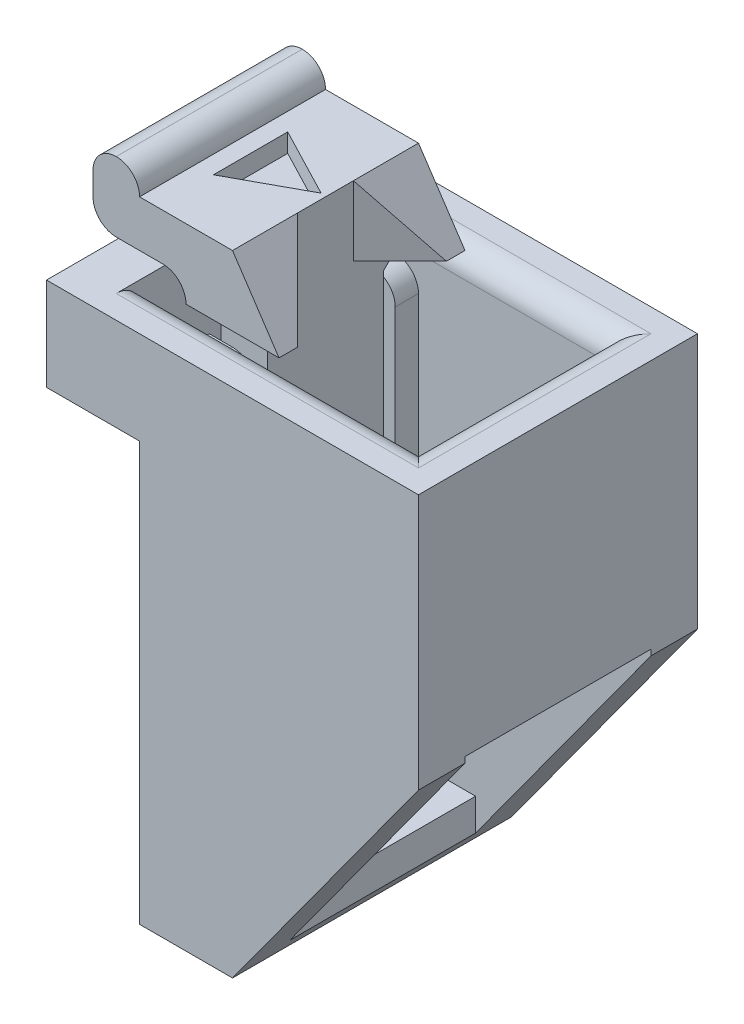
SolidWorks part; units mm, degrees
ref_plane "Front Plane" through (0, 0, 0) normal (0, 0, 1) x (1, 0, 0)
ref_plane "Top Plane" through (0, 0, 0) normal (0, 1, 0) x (1, 0, 0)
ref_plane "Right Plane" through (0, 0, 0) normal (1, 0, 0) x (0, 0, -1)
sketch "BaseSketch" plane through (0, 0, 0) normal (0, 1, 0) x (1, 0, 0)
  line L1 (-6.2677, 3.9685) -> (9.7323, 3.9685)
  line L2 (-6.2677, 3.9685) -> (-6.2677, -8.0315)
  line L3 (-6.2677, -8.0315) -> (9.7323, -8.0315)
  line L4 (9.7323, 3.9685) -> (9.7323, -8.0315)
  dimension "D1" = 16
  dimension "D2" = 12
extrude "BaseExtrude" add sketch "BaseSketch" along normal blind 2
sketch "SlotSketch" plane through (0, 2, 0) normal (0, 1, 0) x (1, 0, 0)
  line L10 (-2.2677, 0.9685) -> (-0.2677, 0.9685)
  line L11 (-2.2677, 1.9685) -> (-4.2677, 1.9685)
  line L12 (-2.2677, 1.9685) -> (-2.2677, 0.9685)
  line L13 (-0.2677, -6.0315) -> (7.7323, -6.0315)
  line L14 (7.7323, -6.0315) -> (7.7323, 1.9685)
  line L15 (-4.2677, -6.0315) -> (7.7323, -6.0315)
  line L16 (-4.2677, 1.9685) -> (-4.2677, -6.0315)
  line L17 (7.7323, 1.9685) -> (-4.2677, 1.9685)
  line L18 (7.7323, -6.0315) -> (7.7323, 1.9685)
  line L19 (-4.2677, -6.0315) -> (-2.2677, -6.0315)
  line L20 (-4.2677, 1.9685) -> (-4.2677, -6.0315)
  line L21 (7.7323, 1.9685) -> (-0.2677, 1.9685)
  line L22 (-0.2677, 1.9685) -> (-0.2677, 0.9685)
  line L23 (-2.2677, -5.0315) -> (-0.2677, -5.0315)
  line L24 (-2.2677, 0.4685) -> (-2.2677, -4.5315)
  line L25 (-2.2677, 0.4685) -> (-0.2677, 0.4685)
  line L26 (-2.2677, 0.4685) -> (-2.2677, -4.5315)
  line L27 (-2.2677, -4.5315) -> (-0.2677, -4.5315)
  line L28 (-0.2677, 0.4685) -> (-0.2677, -4.5315)
  line L29 (-0.2677, 0.4685) -> (-0.2677, -4.5315)
  line L30 (-2.2677, -5.0315) -> (-2.2677, -6.0315)
  line L31 (-0.2677, -5.0315) -> (-0.2677, -6.0315)
  line L33 (-6.2677, 3.9685) -> (9.7323, 3.9685)
  line L34 (-6.2677, 3.9685) -> (-6.2677, -8.0315)
  line L35 (-6.2677, -8.0315) -> (9.7323, -8.0315)
  line L36 (9.7323, 3.9685) -> (9.7323, -8.0315)
  line M5 (-6.2677, 3.9685) -> (-6.2677, -8.0315)
  line M6 (-6.2677, -8.0315) -> (9.7323, -8.0315)
  line M7 (9.7323, -8.0315) -> (9.7323, 3.9685)
  line M8 (9.7323, 3.9685) -> (-6.2677, 3.9685)
  dimension "D2" = 8
  dimension "D3" = 2
  dimension "D4" = 2
  dimension "D5" = 8
  dimension "D6" = 1
  dimension "D7" = 1
  dimension "D8" = 5
  dimension "D9" = 0.5
  dimension "D1" = 2
extrude "FlapExtrude" add sketch "SlotSketch" along normal blind 20.1 contours L25 L28 L27 L24
sketch "HandleBaseSketch" plane through (0, 22.1, 0) normal (0, 1, 0) x (1, 0, 0)
  line L0 (9.7323, 3.9685) -> (-6.2677, 3.9685) construction
  line L1 (-2.2677, 1.9685) -> (-0.2677, 1.9685)
  line L2 (-2.2677, 1.9685) -> (-2.2677, -6.0315)
  line L3 (-2.2677, -6.0315) -> (-0.2677, -6.0315)
  line L4 (-0.2677, 1.9685) -> (-0.2677, -6.0315)
  line L5 (-6.2677, -8.0315) -> (9.7323, -8.0315) construction
  dimension "D1" = 2
  dimension "D2" = 2
extrude "HandleBase" add sketch "HandleBaseSketch" along normal blind 3
sketch "TriangleBaseSketch" plane through (-0.2677, 0, 0) normal (1, 0, 0) x (0, 0, -1)
  line L0 (-6.0315, 22.1) -> (-3.2315, 22.1)
  line L1 (-3.2315, 22.1) -> (-3.2315, 25.1)
  line L2 (-6.0315, 25.1) -> (1.9685, 25.1) construction
  line L3 (-3.2315, 25.1) -> (-6.0315, 25.1)
  line L4 (-6.0315, 25.1) -> (-6.0315, 22.1)
  line L5 (1.9685, 22.1) -> (-0.8315, 22.1)
  line L6 (-0.8315, 22.1) -> (-0.8315, 25.1)
  line L7 (-0.8315, 25.1) -> (1.9685, 25.1)
  line L8 (1.9685, 25.1) -> (1.9685, 22.1)
extrude "PyramidExtrude" add sketch "TriangleBaseSketch" along normal blind 2.8
sketch "PyramidSideCutSketch" plane through (0, 0, -1.9685) normal (0, 0, -1) x (-1, 0, 0)
  line L0 (0.2677, 25.1) -> (0.2677, 22.1)
  line L1 (0.2677, 25.1) -> (-2.5323, 25.1)
  line L2 (-2.5323, 25.1) -> (-2.5323, 22.1)
  line L3 (-2.5323, 22.1) -> (-1.7323, 22.1)
  line L4 (-2.5323, 22.1) -> (2.2677, 22.1) construction
  line L5 (-1.7323, 22.1) -> (0.2677, 25.1)
  dimension "D1" = 2
sketch "PyramidTopCutSketch" plane through (0, 25.1, 0) normal (0, 1, 0) x (1, 0, 0)
  line L0 (-0.2677, -3.2315) -> (2.5323, -6.0315)
  line L1 (2.5323, -6.0315) -> (2.5323, -3.2315)
  line L2 (2.5323, -3.2315) -> (-0.2677, -3.2315)
  line L3 (-0.2677, -0.8315) -> (2.5323, 1.9685)
  line L4 (2.5323, 1.9685) -> (2.5323, -0.8315)
  line L5 (2.5323, -0.8315) -> (-0.2677, -0.8315)
extrude "PyramidTopCut" cut sketch "PyramidTopCutSketch" against normal blind 3
extrude "PyramidSideCut" cut sketch "PyramidSideCutSketch" against normal through all contours L1 L2 L3 L5
extrude "Boss-Extrude5" add sketch "SlotSketch<6>" along normal blind 3 contours L31 L23 L30 L19 L20 L11 L12 L10 L22 L21 L18 L13 M8 M5 M6 M7 | L12 L10 L22 L21 L18 L13 L31 L23 L30 L19 L20 L11 | L33 L36 L35 L34 region at (-1.2677, 2, -1.4685) region at (-1.2677, 2, 5.5315) region at (1.7323, 2, -3.7685)
sketch "SlotSketch<6>" plane through (0, 2, 0) normal (0, 1, 0) x (1, 0, 0) same geometry as "SlotSketch"
extrude "Sides" add sketch "SlotSketch<7>" along normal blind 20 contours L11 L20 L19 L30 L23 L31 L13 L18 L21 L22 L10 L12 | L33 L36 L35 L34
sketch "SlotSketch<7>" plane through (0, 2, 0) normal (0, 1, 0) x (1, 0, 0) same geometry as "SlotSketch"
sketch "Sketch7" plane through (-0.2677, 0, 0) normal (1, 0, 0) x (0, 0, -1)
  line L0 (-5.0315, 22) -> (-5.0315, 2) construction
  line L1 (-6.0315, 22) -> (-5.0315, 22)
  line L2 (-6.0315, 22) -> (-6.0315, 20.4974)
  line L3 (-6.0315, 20.4974) -> (-5.0315, 20.4974)
  line L4 (-5.0315, 22) -> (-5.0315, 20.4974)
  line L5 (1.9685, 22) -> (1.9685, 2) construction
  line L6 (0.9685, 22) -> (1.9685, 22)
  line L7 (0.9685, 22) -> (0.9685, 20.4974)
  line L8 (0.9685, 20.4974) -> (1.9685, 20.4974)
  line L9 (1.9685, 22) -> (1.9685, 20.4974)
extrude "WallClearanceCut" cut sketch "Sketch7" against normal blind 2
sketch "BaseTriangleCutSketch" plane through (0, 0, 8.0315) normal (0, 0, 1) x (1, 0, 0)
  line L0 (9.7323, 0) -> (1.7323, 0)
  line L1 (-6.2677, 0) -> (9.7323, 0) construction
  line L2 (1.7323, 0) -> (9.7323, 11)
  line L3 (9.7323, 22) -> (9.7323, 0) construction
  line L4 (9.7323, 11) -> (9.7323, 0)
extrude "BaseTriangleCut" cut sketch "BaseTriangleCutSketch" against normal through all
sketch "Sketch9" plane through (-2.2677, 0, 0) normal (-1, 0, 0) x (0, 0, 1)
  line L0 (6.0315, 25.1) -> (6.0315, 22.1) construction
  line L1 (-1.9685, 25.1) -> (6.0315, 25.1)
  line L2 (-1.9685, 25.1) -> (-1.9685, 23.1)
  line L3 (-1.9685, 23.1) -> (6.0315, 23.1)
  line L4 (6.0315, 25.1) -> (6.0315, 23.1)
extrude "Handle" add sketch "Sketch9" along normal blind 4
sketch "Sketch10" plane through (0, 25.1, 0) normal (0, 1, 0) x (1, 0, 0)
  line L0 (-0.2677, 1.9685) -> (-6.2677, 1.9685) construction
  line L1 (-6.2677, -6.0315) -> (-4.2659, -6.0315)
  line L2 (-6.2677, -6.0315) -> (-6.2677, 1.9685)
  line L3 (-6.2677, 1.9685) -> (-4.2659, 1.9685)
  line L4 (-4.2659, -6.0315) -> (-4.2659, 1.9685)
extrude "Boss-Extrude8" add sketch "Sketch10" along normal blind 1
sketch "WashHoleSketch" plane through (-6.2677, 0, 0) normal (-1, 0, 0) x (0, 0, 1)
  line L0 (-3.9685, 22) -> (-3.9685, 0) construction
  line L1 (-1.9685, 18) -> (6.0315, 18)
  line L2 (-1.9685, 18) -> (-1.9685, 4)
  line L3 (-1.9685, 4) -> (6.0315, 4)
  line L4 (6.0315, 18) -> (6.0315, 4)
  line L5 (8.0315, 22) -> (8.0315, 0) construction
  line L6 (-3.9685, 22) -> (8.0315, 22) construction
  line L7 (-3.9685, 0) -> (8.0315, 0) construction
  dimension "D1" = 2
  dimension "D2" = 2
  dimension "D3" = 4
  dimension "D4" = 4
extrude "WashHole" cut sketch "WashHoleSketch" against normal blind 2
fillet "Fillet1" radius 1 10 edges at (1.7323, 22, -1.9685) (1.7323, 22, 6.0315) (7.7323, 22, 2.0315) (-2.2677, 2, 2.0315) (-2.2677, 23.1, 2.0315) (-6.2677, 23.1, 2.0315) (-4.2659, 26.1, 2.0315) (-6.2677, 26.1, 2.0315) (-0.2677, 20.4974, -1.4685) (-0.2677, 20.4974, 5.5315)
sketch "MarkerSketch" plane through (0, 25.1, 0) normal (0, 1, 0) x (1, 0, 0)
  line L0 (-0.4994, -1.9893) -> (-3.4984, -0.4264)
  line L1 (-3.4984, -0.4264) -> (-3.4984, -3.6225)
  line L2 (-3.4984, -3.6225) -> (-0.4994, -1.9893)
extrude "Cut-Extrude6" cut sketch "MarkerSketch" against normal blind 0.8
sketch "Sketch11" plane through (7.7323, 0, 0) normal (-1, 0, 0) x (0, 0, 1)
  line L1 (6.0315, 8.25) -> (-1.9685, 8.25)
  line L2 (6.0315, 8.25) -> (6.0315, 11.25)
  line L3 (6.0315, 11.25) -> (-1.9685, 11.25)
  line L4 (-1.9685, 8.25) -> (-1.9685, 11.25)
  dimension "D1" = 3
extrude "Cut-Extrude7" cut sketch "Sketch11" against normal blind 10
sketch "Sketch12" plane through (0, 2, 0) normal (0, 1, 0) x (1, 0, 0)
  line L0 (-0.2677, -6.0315) -> (3.1868, -6.0315) construction
  line L1 (3.1868, 1.9685) -> (2.1868, 1.9685)
  line L2 (3.1868, 1.9685) -> (3.1868, -6.0315)
  line L3 (3.1868, -6.0315) -> (2.1868, -6.0315)
  line L4 (2.1868, 1.9685) -> (2.1868, -6.0315)
  dimension "D1" = 1
extrude "Cut-Extrude8" cut sketch "Sketch12" against normal blind 10
chamfer "Chamfer1" distance 1 angle 45 2 edges
sketch "Sketch14" plane through (0, 0, 8.0315) normal (0, 0, 1) x (1, 0, 0)
  line L0 (-6.2677, 0) -> (1.7323, 0) construction
  line L1 (-6.2677, 18) -> (-2.2677, 18)
  line L2 (-6.2677, 18) -> (-6.2677, 0)
  line L3 (-6.2677, 0) -> (-2.2677, 0)
  line L4 (-2.2677, 18) -> (-2.2677, 0)
extrude "Cut-Extrude9" cut sketch "Sketch14" against normal through all
